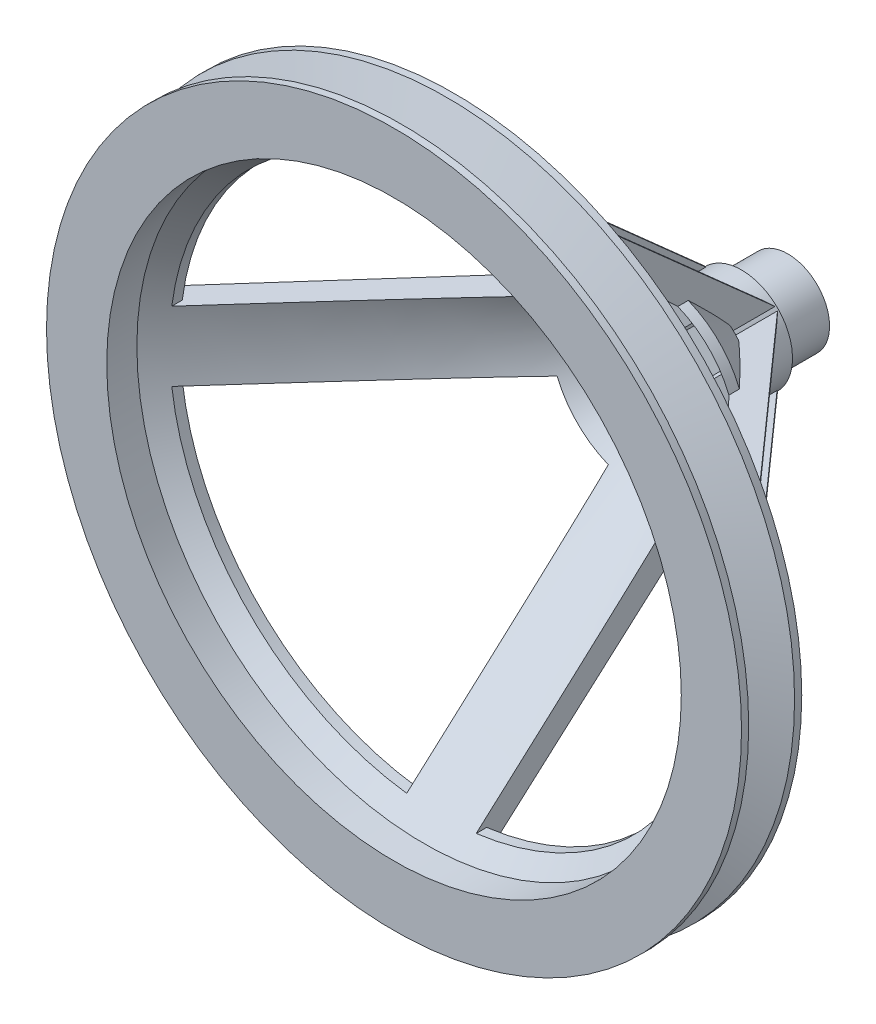
SolidWorks part; units mm, degrees
ref_plane "前视基准面" through (0, 0, 0) normal (0, 0, 1) x (1, 0, 0)
ref_plane "上视基准面" through (0, 0, 0) normal (0, 1, 0) x (1, 0, 0)
ref_plane "右视基准面" through (0, 0, 0) normal (1, 0, 0) x (0, 0, -1)
other "Configuration Table"
sketch "草图3" plane through (0, 0, 0) normal (1, 0, 0) x (0, 0, -1)
  line L0 (-6.5, 62) -> (6.5, 62)
  line L1 (6.5, 62) -> (6.5, 75)
  line L2 (6.5, 75) -> (4.95, 75)
  line L3 (4.95, 75) -> (1.2657, 64.3)
  line L4 (1.2657, 64.3) -> (-1.2657, 64.3)
  line L6 (0, 0) -> (0, 73.8652) construction
  line L7 (-4.95, 75) -> (-1.2657, 64.3)
  line L8 (-6.5, 75) -> (-4.95, 75)
  line L9 (-6.5, 62) -> (-6.5, 75)
  line L10 (-4.25, 72.9671) -> (4.25, 72.9671)
  line L11 (0, 0) -> (-31.5211, 0) construction
  dimension "D1" = 38
  dimension "D2" = 13
  dimension "D3" = 62
  dimension "D4" = 9.9
  dimension "D5" = 10.7
  dimension "D6" = 75
  dimension "D7" = 8.5
revolve "旋转1" add sketch "草图3" angle 360 about L11
sketch "草图5" plane through (0, 0, -6.5) normal (0, 0, -1) x (-1, 0, 0)
  circle A0 centre (0, 0) radius 11
  dimension "D1" = 22
extrude "凸台-拉伸1" add sketch "草图5" along normal blind 10 from offset 52 separate body
sketch "草图6" plane through (0, 0, -68.5) normal (0, 0, -1) x (-1, 0, 0)
  circle A0 centre (0, 0) radius 9
  dimension "D1" = 18
extrude "凸台-拉伸2" add sketch "草图6" along normal blind 10
sketch "草图7" plane through (0, 0, -78.5) normal (0, 0, -1) x (-1, 0, 0)
  line L0 (0.3536, 6.0104) -> (-0.3536, 6.0104)
  line L1 (6.0104, 0.3536) -> (0.3536, 6.0104)
  line L2 (-0.3536, 6.0104) -> (-6.0104, 0.3536)
  line L3 (-6.0104, -0.3536) -> (-0.3536, -6.0104)
  line L4 (0.3536, -6.0104) -> (6.0104, -0.3536)
  line L5 (6.0104, -0.3536) -> (6.0104, 0.3536)
  line L6 (-0.3536, -6.0104) -> (0.3536, -6.0104)
  line L7 (-6.0104, 0.3536) -> (-6.0104, -0.3536)
  circle A0 centre (0, 0) radius 4.5 construction
  point P2 (6.364, 0)
  point P3 (0, 6.364)
  point P4 (-6.364, 0)
  point P5 (0, -6.364)
  dimension "D1" = 9
extrude "切除-拉伸1" cut sketch "草图7" against normal through all both and the other way through all
sketch "草图10" plane through (0, 0, 0) normal (1, 0, 0) x (0, 0, -1)
  line L0 (58.5, 10) -> (0, 62)
  line L1 (58.5, 11) -> (58.5, -11) construction
  line L3 (6.5, 62) -> (-6.5, 62) construction
  line L4 (6.5, -75) -> (6.5, 75) construction
  line L5 (58.5, 10) -> (58.5, 12.0069)
  line L6 (58.5, 12.0069) -> (2.2578, 62)
  line L7 (2.2578, 62) -> (0, 62)
  line L8 (0, 0) -> (45.0785, 0) construction
  dimension "D1" = 10
  dimension "D2" = 6.5
  dimension "D3" = 1.5
revolve "旋转2" add sketch "草图10" angle 360 about L8
fillet "圆角1" radius 2 1 edges at (62, 0, -2.2578)
sketch "草图14" plane through (0, 0, 0) normal (0, 1, 0) x (1, 0, 0)
  line L0 (11, 62.6432) -> (62.2409, 4.9972)
  line L1 (58.6811, 5.9915) -> (12.0069, 58.5) construction
  line L2 (11, 58.5) -> (11, 68.5) construction
  dimension "D1" = 2
rib "筋1" sketch "草图14" sketch "草图14" thickness 1 extrusion direction parallel to sketch draft on no parameters "D1"=1
ref_plane "基准面2" through (0, 7, 0) normal (0, 1, 0) x (1, 0, 0)
sketch "草图15" plane through (0, 7, 0) normal (0, 1, 0) x (1, 0, 0)
  line L0 (7.8009, 68.5) -> (64.3084, 4.929)
  line L2 (10.9886, 62.656) -> (61.5038, 5.8264) construction
  dimension "D1" = 1.5
rib "筋2" sketch "草图15" sketch "草图15" thickness 1 extrusion direction parallel to sketch draft on no parameters "D1"=1
mirror "镜向1" about plane through (0, 0, 0) normal (0, 1, 0) of "筋2"
pattern_circular "阵列(圆周)2" count 4 over 360 about axis through (0, 0, 0) along (0, 0, 1) of "镜向1", "筋1", "筋2"
sketch "草图16" plane through (0, 0, 0) normal (0, 0, 1) x (1, 0, 0)
  line L0 (-7.5, -9.3764) -> (-7.5, -58.1999) construction
  line L1 (-58.1999, -7.5) -> (-9.3764, -7.5) construction
  line L2 (-7.5, -18.5405) -> (-7.5, -58.1999)
  line L3 (-58.1999, -7.5) -> (-18.5405, -7.5)
  arc A0 (-58.1999, -7.5) -> (-7.5, -58.1999) centre (0, 0) ccw construction
  arc A1 (-58.1999, -7.5) -> (-7.5, -58.1999) centre (0, 0) ccw
  arc A2 (-18.5405, -7.5) -> (-7.5, -18.5405) centre (0, 0) ccw
  dimension "D1" = 40
extrude "切除-拉伸2" cut sketch "草图16" against normal through all both
pattern_circular "阵列(圆周)3" count 4 over 360 about axis through (0, 0, 6.5) along (0, 0, -1) of "切除-拉伸2"
